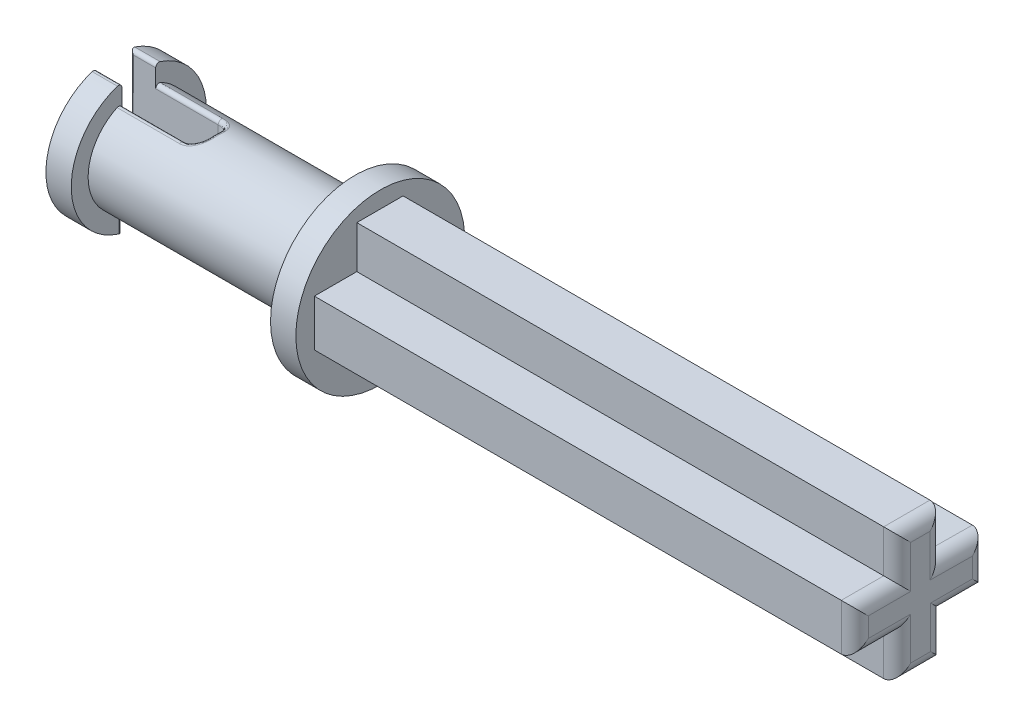
SolidWorks part; units mm, degrees
ref_plane "Front Plane" through (0, 0, 0) normal (0, 0, 1) x (1, 0, 0)
ref_plane "Top Plane" through (0, 0, 0) normal (0, 1, 0) x (1, 0, 0)
ref_plane "Right Plane" through (0, 0, 0) normal (1, 0, 0) x (0, 0, -1)
sketch "CircularBase" plane through (0, 0, 0) normal (0, 0, 1) x (1, 0, 0)
  line L0 (-5.0594, 0) -> (7.0797, 0) construction
  line L1 (0, 0) -> (0, 0.5)
  line L2 (0, 0.5) -> (-2, 0.5)
  line L3 (-2, 0.5) -> (-2, 2)
  line L4 (-2, 2) -> (-1.25, 2)
  line L5 (-1.25, 2) -> (-1.25, 1.5)
  line L6 (-1.25, 1.5) -> (5.15, 1.5)
  line L7 (5.15, 1.5) -> (5.15, 2.5)
  line L8 (5.15, 2.5) -> (5.9, 2.5)
  line L9 (5.9, 2.5) -> (5.9, 0)
  line L11 (0, 0) -> (5.9, 0)
  line L12 (7.0797, 0) -> (14.1483, 0) construction
  dimension "D1" = 0.75
  dimension "D2" = 0.75
  dimension "D3" = 1
  dimension "D4" = 0.5
  dimension "D5" = 1.5
  dimension "D6" = 0.5
  dimension "D7" = 2.5
  dimension "D8" = 2
  dimension "D9" = 5.9
revolve "CircularBaseRevolve" add sketch "CircularBase" angle 360 about L12
ref_plane "BasePlane" through (-2, 0, 0) normal (-1, 0, 0) x (0, 0, 1)
sketch "NotchCutSketc" plane through (-2, 0, 0) normal (-1, 0, 0) x (0, 0, 1)
  line L0 (0, 2) -> (0, -2) construction
  line L1 (-0.5, 0) -> (-0.5, 1.9365)
  line L2 (-0.5, 1.9365) -> (0.5, 1.9365)
  line L3 (-0.5, 0) -> (-0.5, -1.9365)
  line L4 (-0.5, -1.9365) -> (0.5, -1.9365)
  line L5 (0.5, 0) -> (0.5, -1.9365)
  line L6 (0.5, 0) -> (0.5, 1.9365)
  circle A0 centre (0, 0) radius 2 construction
  circle A1 centre (0, 0) radius 0.5 construction
  circle A2 centre (0, 0) radius 0.5 construction
  point P15 (0, -1.9365)
  point P17 (0, 1.9365)
extrude "NotchCut" cut sketch "NotchCutSketc" against normal blind 3
fillet "InsideNotchFillet1" radius 0.4 1 edges at (1, 0, -0.5) type face fillet first side face at (-0.875, 0, -0.5) second side face at (1, 0, 0)
fillet "InsideNotchFillet2" radius 0.4 1 edges at (1, 0, 0.5) type face fillet first side face at (-0.875, 0, 0.5) second side face at (1, 0, 0.2021)
fillet "OutsideNotchFillet" radius 0.1 16 edges at (-2, 0, 0.5) (-2, 0, -0.5) (-0.325, -1.4142, -0.5) (0.915, -1.4594, -0.3465) (1, -1.5, 0) (0.8413, -1.4403, 0.419) (-0.325, 1.4142, 0.5) (0.915, 1.4594, 0.3465) (1, 1.5, 0) (0.8413, 1.4403, -0.419) (-1.625, 1.9365, 0.5) (-1.625, 1.9365, -0.5) (-1.625, -1.9365, -0.5) (-0.325, -1.4142, 0.5) (-0.325, 1.4142, -0.5) (-1.25, -1.6754, 0.5)
ref_plane "TopBasePlane" through (5.9, 0, 0) normal (1, 0, 0) x (0, 0, -1)
sketch "TopCircularBaseExtrudeSketch" plane through (5.9, 0, 0) normal (1, 0, 0) x (0, 0, -1)
  line L16 (-1.9515, -0.6295) -> (-1.9515, 0.7505)
  line L17 (-1.9515, 0.7505) -> (-0.695, 0.7505)
  line L18 (0.675, 2.007) -> (-0.695, 2.007)
  line L19 (-0.695, 2.007) -> (-0.695, 0.7505)
  line L20 (1.9315, -0.6419) -> (1.9315, 0.7381)
  line L21 (1.9315, 0.7381) -> (0.675, 0.7505)
  line L22 (0.675, 2.007) -> (0.675, 0.7505)
  line L23 (1.9315, -0.6419) -> (0.695, -0.6419)
  line L24 (0.695, -1.886) -> (0.695, -0.6419)
  line L25 (-1.9515, -0.6295) -> (-0.695, -0.6295)
  line L26 (-0.695, -1.886) -> (-0.695, -0.6295)
  line L27 (0.695, -1.886) -> (-0.695, -1.886)
  point P16 (1.9315, 0.0481)
  dimension "D1" = 1.37
  dimension "D2" = 1.38
  dimension "D3" = 1.38
extrude "TopCircularBaseExtrude" add sketch "TopCircularBaseExtrudeSketch" along normal blind 16
fillet "TopCircularBaseFillet" radius 0.4 12 edges at (21.9, 1.3788, 0.695) (21.9, 1.3788, -0.675) (21.9, 0.7505, 1.3233) (21.9, 0.7443, -1.3033) (21.9, 0.0481, -1.9315) (21.9, -0.6419, -1.3133) (21.9, -1.2639, -0.695) (21.9, -1.886, 0) (21.9, 0.0605, 1.9515) (21.9, 2.007, 0.01) (21.9, -0.6295, 1.3233) (21.9, -1.2577, 0.695)
